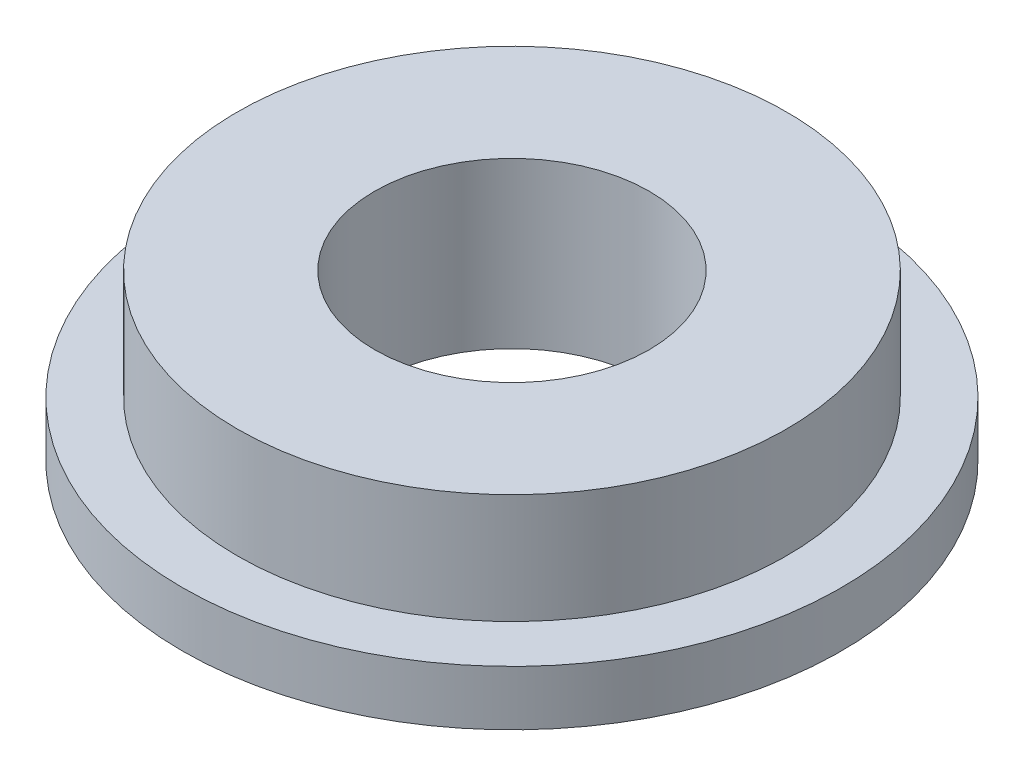
SolidWorks part; units mm, degrees
ref_plane "前视基准面" through (0, 0, 0) normal (0, 0, 1) x (1, 0, 0)
ref_plane "上视基准面" through (0, 0, 0) normal (0, 1, 0) x (1, 0, 0)
ref_plane "右视基准面" through (0, 0, 0) normal (1, 0, 0) x (0, 0, -1)
sketch "草图1" plane through (0, 0, 0) normal (0, 1, 0) x (1, 0, 0)
  circle A0 centre (0, 0) radius 3.6
  circle A1 centre (0, 0) radius 3
  circle A2 centre (0, 0) radius 1.5
  dimension "D1" = 7.2
  dimension "D2" = 6
  dimension "D3" = 3
extrude "凸台-拉伸1" add sketch "草图1" along normal blind 0.6 contours A1 | A0
extrude "凸台-拉伸2" add sketch "草图1<3>" along normal blind 1.8 contours A1 A2 region at (-2.9151, 0, 0)
sketch "草图1<3>" plane through (0, 0, 0) normal (0, 1, 0) x (1, 0, 0) same geometry as "草图1"
